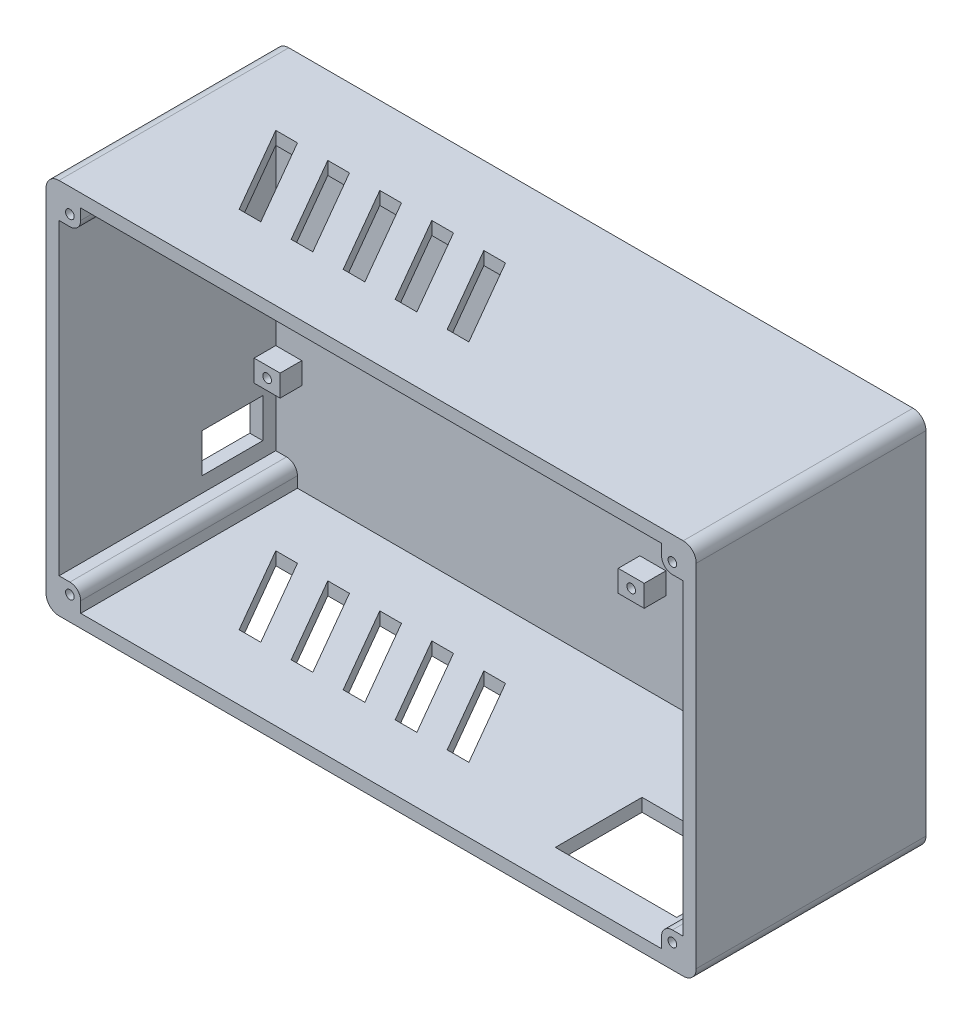
SolidWorks part; units mm, degrees
ref_plane "Front Plane" through (0, 0, 0) normal (0, 0, 1) x (1, 0, 0)
ref_plane "Top Plane" through (0, 0, 0) normal (0, 1, 0) x (1, 0, 0)
ref_plane "Right Plane" through (0, 0, 0) normal (1, 0, 0) x (0, 0, -1)
sketch "Sketch1" plane through (0, 0, 0) normal (0, 0, 1) x (1, 0, 0)
  line L1 (0, 0) -> (150, 0)
  line L2 (0, 0) -> (0, 87)
  line L3 (0, 87) -> (150, 87)
  line L4 (150, 0) -> (150, 87)
  dimension "D1" = 150
  dimension "D2" = 87
extrude "Body_frame" add sketch "Sketch1" along normal blind 53
fillet "body_edges" radius 3 4 edges at (150, 0, 26.5) (150, 87, 26.5) (0, 0, 26.5) (0, 87, 26.5)
shell "Shell1" thickness 3 removed face at (75, 43.5, 53)
sketch "Sketch3" plane through (0, 0, 3) normal (0, 0, 1) x (1, 0, 0)
  line L0 (3, 81.5) -> (8, 81.5) construction
  line L1 (3, 84) -> (8, 84)
  line L2 (3, 84) -> (3, 79)
  line L3 (3, 79) -> (5.5, 79)
  line L4 (8, 84) -> (8, 81.5)
  line L5 (5.5, 84) -> (5.5, 79) construction
  circle A0 centre (5.5, 81.5) radius 1
  arc A1 (8, 81.5) -> (5.5, 79) centre (5.5, 81.5) cw
  dimension "D3" = 2
extrude "screw_hole" add sketch "Sketch3" along normal blind 50
ref_plane "Plane5" through (75, 0, 0) normal (-1, 0, 0) x (0, 0, 1)
ref_plane "Plane6" through (0, 43.5, 0) normal (0, 1, 0) x (1, 0, 0)
mirror "Mirror1" about plane through (75, 0, 0) normal (-1, 0, 0) of "screw_hole"
mirror "Mirror2" about plane through (0, 43.5, 0) normal (0, 1, 0) of "Mirror1", "screw_hole"
sketch "Sketch4" plane through (0, 0, 3) normal (0, 0, 1) x (1, 0, 0)
  line L0 (3, 79) -> (147, 79) construction
  line L1 (3, 74) -> (147, 74) construction
  line L2 (3, 79) -> (3, 8) construction
  line L3 (147, 8) -> (147, 79) construction
  line L4 (3, 24) -> (147, 24) construction
  line L5 (3, 79) -> (3, 8) construction
  line L6 (3, 29) -> (147, 29) construction
  line L7 (147, 8) -> (147, 79) construction
  line L8 (9, 84) -> (9, 24) construction
  line L9 (142, 84) -> (8, 84) construction
  line L10 (93, 79) -> (93, 24) construction
  line L11 (3, 79) -> (93, 79) construction
  line L12 (87, 79) -> (87, 24) construction
  line L13 (3, 76.5) -> (9, 76.5) construction
  line L14 (3, 79) -> (9, 79)
  line L15 (3, 79) -> (3, 74)
  line L16 (3, 74) -> (9, 74)
  line L17 (9, 79) -> (9, 74)
  line L18 (87, 79) -> (93, 79)
  line L19 (87, 79) -> (87, 74)
  line L20 (87, 74) -> (93, 74)
  line L21 (93, 79) -> (93, 74)
  line L22 (3, 29) -> (9, 29)
  line L23 (3, 29) -> (3, 24)
  line L24 (3, 24) -> (9, 24)
  line L25 (9, 29) -> (9, 24)
  line L26 (93, 24) -> (87, 24)
  line L27 (93, 24) -> (93, 29)
  line L28 (93, 29) -> (87, 29)
  line L29 (87, 24) -> (87, 29)
  line L30 (9, 76.5) -> (93, 76.5) construction
  line L31 (3, 26.5) -> (93, 26.5) construction
  line L32 (6, 24) -> (6, 79) construction
  line L33 (90, 79) -> (90, 24) construction
  circle A0 centre (6, 76.5) radius 1
  circle A1 centre (6, 26.5) radius 1
  circle A2 centre (90, 26.5) radius 1
  circle A3 centre (90, 76.5) radius 1
  dimension "D7" = 2
  dimension "D8" = 2
  dimension "D9" = 2
  dimension "D10" = 2
  dimension "D1" = 5
  dimension "D2" = 55
  dimension "D3" = 5
  dimension "D4" = 6
  dimension "D5" = 90
  dimension "D6" = 6
extrude "Boss-Extrude3" add sketch "Sketch4" along normal blind 5
sketch "Sketch5" plane through (3, 0, 0) normal (1, 0, 0) x (0, 0, -1)
  line L0 (-53, 8) -> (-20, 8) construction
  line L1 (0, 3) -> (0, 84) construction
  line L2 (-6, 3) -> (-6, 8) construction
  line L3 (-53, 3) -> (0, 3) construction
  line L4 (-53, 87) -> (0, 87) construction
  line L5 (-51.9185, 20.5) -> (-20, 20.5) construction
  line L6 (-20, 11.5) -> (-6, 11.5) construction
  line L12 (-6, 20.5) -> (-6, 87) construction
  line L17 (-6, 8) -> (0, 8) construction
  line L18 (-6, 11.5) -> (-20, 11.5)
  line L19 (-6, 11.5) -> (-6, 20.5)
  line L20 (-6, 20.5) -> (-20, 20.5)
  line L21 (-20, 11.5) -> (-20, 20.5)
  dimension "D1" = 6
  dimension "D2" = 12.5
  dimension "D3" = 14
  dimension "D4" = 3.5
  dimension "D5" = 9
extrude "switch" cut sketch "Sketch5" against normal through all
sketch "Sketch6" plane through (0, 0, 0) normal (0, -1, 0) x (1, 0, 0)
  line L0 (147, 25) -> (3, 25) construction
  line L1 (147, 0) -> (147, 53) construction
  line L2 (3, 53) -> (3, 0) construction
  line L3 (109.5, 0) -> (109.5, 53) construction
  line L4 (3, 0) -> (147, 0) construction
  line L5 (3, 53) -> (147, 53) construction
  line L6 (147, 53) -> (147, 0) construction
  line L7 (147, 45) -> (109.5, 45) construction
  line L8 (137.5, 45) -> (137.5, 25) construction
  line L10 (109.5, 45) -> (137.5, 45)
  line L11 (109.5, 45) -> (109.5, 25)
  line L12 (109.5, 25) -> (137.5, 25)
  line L13 (137.5, 45) -> (137.5, 25)
  dimension "D1" = 8
  dimension "D2" = 20
  dimension "D3" = 9.5
  dimension "D4" = 28
extrude "AC_IN" cut sketch "Sketch6" against normal blind 3
sketch "Sketch8" plane through (0, 0, 0) normal (-1, 0, 0) x (0, 0, 1)
  line L1 (3.5, 87) -> (3.5, 0) construction
  line L2 (0, 87) -> (53, 87) construction
  line L3 (53, 0) -> (0, 0) construction
  line L4 (18.5, 87) -> (18.5, 52.4394) construction
  line L5 (14.5, 84) -> (14.5, 46.6928) construction
  line L6 (53, 84) -> (0, 84) construction
  line L7 (22.5, 84) -> (22.5, 46.6928) construction
  line L8 (22.5, 79) -> (14.5, 79) construction
  line L9 (22.5, 55.9284) -> (14.5, 55.9284) construction
  line L10 (22.5, 70.5) -> (14.5, 70.5) construction
  line L11 (22.5, 57.5) -> (14.5, 57.5) construction
  line L13 (22.5, 70.5) -> (14.5, 70.5)
  line L14 (22.5, 70.5) -> (22.5, 57.5)
  line L15 (22.5, 57.5) -> (14.5, 57.5)
  line L16 (14.5, 70.5) -> (14.5, 57.5)
  dimension "D1" = 3.5
  dimension "D2" = 15
  dimension "D3" = 4
  dimension "D4" = 4
  dimension "D5" = 5
  dimension "D6" = 8.5
  dimension "D7" = 13
extrude "Program_port" cut sketch "Sketch8" against normal blind 3
sketch "Sketch9" plane through (0, 0, 0) normal (0, -1, 0) x (1, 0, 0)
  line L0 (18, 18) -> (23, 18) construction
  line L3 (29.547, 38) -> (34.547, 38) construction
  line L4 (3, 0) -> (147, 0) construction
  line L5 (3, 53) -> (147, 53) construction
  line L7 (18, 18) -> (23, 18)
  line L8 (18, 18) -> (29.547, 38)
  line L9 (23, 18) -> (34.547, 38)
  line L10 (29.547, 38) -> (34.547, 38)
  dimension "D1" = 18
  dimension "D2" = 15
  dimension "D4" = 5
extrude "Cut-Extrude1" cut sketch "Sketch9" against normal through all
pattern_linear "LPattern1" count 5 spacing 12 along (1, 0, 0) of "Cut-Extrude1"
